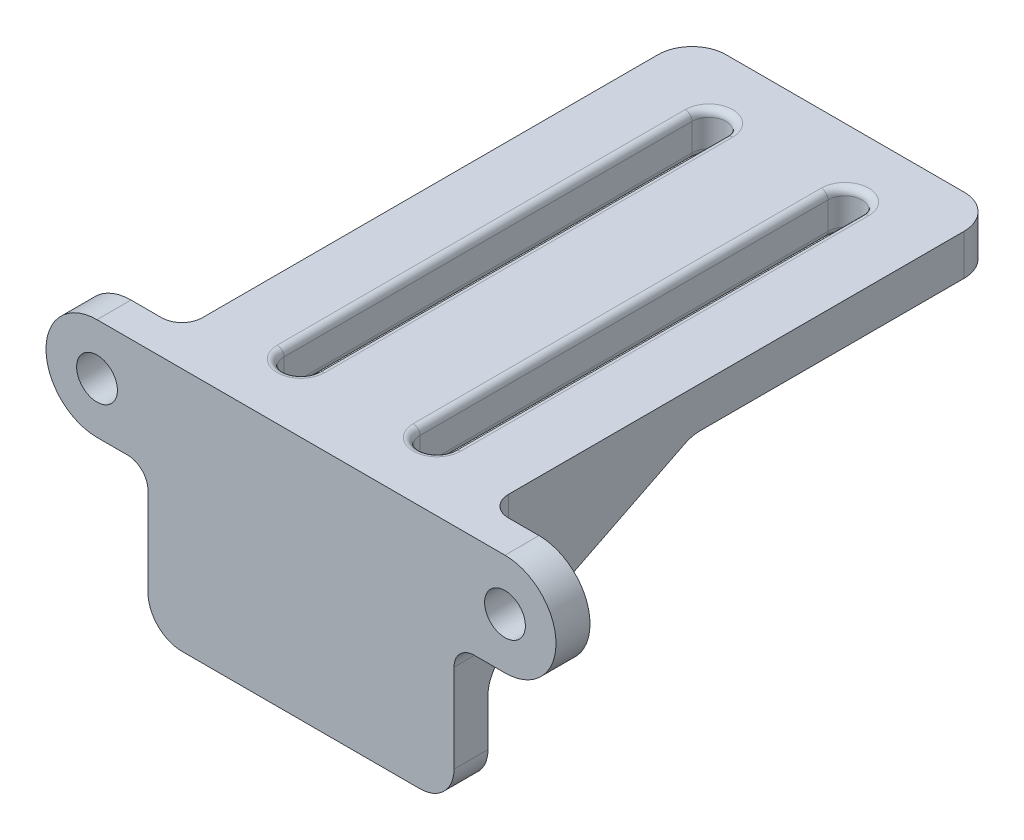
SolidWorks part; units mm, degrees
ref_plane "Piano frontale" through (0, 0, 0) normal (0, 0, 1) x (1, 0, 0)
ref_plane "Piano superiore" through (0, 0, 0) normal (0, 1, 0) x (1, 0, 0)
ref_plane "Piano destro" through (0, 0, 0) normal (1, 0, 0) x (0, 0, -1)
sketch "Schizzo1" plane through (0, 0, 0) normal (0, 0, 1) x (1, 0, 0)
  line L1 (-22.5, 15) -> (22.5, 15)
  line L2 (-22.5, 15) -> (-22.5, -15)
  line L3 (-22.5, -15) -> (22.5, -15)
  line L4 (22.5, 15) -> (22.5, -15)
  line L5 (-22.5, 15) -> (22.5, -15) construction
  line L6 (-22.5, -15) -> (22.5, 15) construction
  point P0 (0, 0)
  dimension "D1" = 45
  dimension "D2" = 30
extrude "Estrusione-Estrusione1" add sketch "Schizzo1" along normal blind 5
sketch "Schizzo4" plane through (0, 15, 0) normal (0, 1, 0) x (1, 0, 0)
  line L1 (22.5, -5) -> (-22.5, -5)
  line L2 (22.5, -5) -> (22.5, 75)
  line L3 (22.5, 75) -> (-22.5, 75)
  line L4 (-22.5, -5) -> (-22.5, 75)
  dimension "D1" = 45
  dimension "D2" = 80
extrude "Estrusione-Estrusione2" add sketch "Schizzo4" along normal blind 6
sketch "Schizzo5" plane through (0, 21, 0) normal (0, 1, 0) x (1, 0, 0)
  line L0 (-10, 37.5433) -> (-10, 50037.5433) construction
  line L1 (0, 75) -> (0, -49925) construction
  line L2 (22.5, 75) -> (-22.5, 75) construction
  line L3 (10, 71.372) -> (10, -49928.628) construction
  line L4 (-20, 35) -> (49980, 35) construction
  line L5 (-22.5, 75) -> (-22.5, -5) construction
  line L6 (-10, 65) -> (-10, 5) construction
  line L7 (-7.5, 65) -> (-7.5, 5)
  line L8 (-12.5, 65) -> (-12.5, 5)
  line L9 (10, 65) -> (10, 5) construction
  line L10 (7.5, 65) -> (7.5, 5)
  line L11 (12.5, 65) -> (12.5, 5)
  arc A0 (-7.5, 65) -> (-12.5, 65) centre (-10, 65) ccw
  arc A1 (-12.5, 5) -> (-7.5, 5) centre (-10, 5) ccw
  arc A2 (7.5, 65) -> (12.5, 65) centre (10, 65) cw
  arc A3 (12.5, 5) -> (7.5, 5) centre (10, 5) cw
  point P6 (0, 75)
  point P13 (-22.5, 35)
  point P16 (-10, 35)
  point P23 (10, 35)
  dimension "D1" = 10
  dimension "D2" = 10
  dimension "D3" = 5
  dimension "D4" = 60
extrude "Taglio-Estrusione1" cut sketch "Schizzo5" against normal through all
fillet "Raccordo1" radius 6 1 edges at (0, 15, 0)
sketch "Schizzo6" plane through (-22.5, 0, 0) normal (-1, 0, 0) x (0, 0, 1)
  line L0 (-30, 15) -> (0, 0)
  line L1 (5, 21) -> (-30, 21)
  line L2 (5, 21) -> (5, 0)
  line L3 (5, 0) -> (-30, 0)
  line L4 (-30, 21) -> (-30, 0)
  line L5 (-75, 15) -> (-6, 15) construction
  line M3 (-75, 15) -> (-6, 15)
  arc M4 (-6, 15) -> (0, 9) centre (-6, 9) cw
  line M5 (0, 9) -> (0, -15)
  line M7 (5, -15) -> (5, 21)
  line M8 (5, 21) -> (-75, 21)
  dimension "D1" = 21
  dimension "D2" = 35
extrude "Estrusione-Estrusione3" add sketch "Schizzo6" against normal blind 3 contours L0 M3 M5 M4 | L4 L3 M8 M3 M4 M5 M7 region at (-22.5, 9.8699, -10.3079) region at (-22.5, 15.1952, -8.3623)
sketch "Schizzo8" plane through (22.5, 0, 0) normal (1, 0, 0) x (0, 0, -1)
  line L0 (0, 0) -> (30, 15)
  line L1 (-5, 21) -> (30, 21)
  line L2 (-5, 21) -> (-5, 0)
  line L3 (-5, 0) -> (30, 0)
  line L4 (30, 21) -> (30, 0)
  line M3 (0, -15) -> (0, 9)
  arc M4 (0, 9) -> (6, 15) centre (6, 9) cw
  line M5 (6, 15) -> (75, 15)
  dimension "D1" = 21
  dimension "D2" = 35
extrude "Estrusione-Estrusione4" add sketch "Schizzo8" against normal blind 3 contours L0 M3 M5 M4 region at (22.5, 9.8699, -10.3079)
fillet "Raccordo2" radius 5 8 edges at (21, 15, -30) (21, 0, 0) (22.5, -15, 2.5) (-22.5, -15, 2.5) (-21, 15, -30) (-21, 0, 0) (-22.5, 18, -75) (22.5, 18, -75)
sketch "Schizzo10" plane through (0, 0, 5) normal (0, 0, 1) x (1, 0, 0)
  line L0 (0, 21) -> (-50000, 21) construction
  line L1 (-22.5, 21) -> (22.5, 21) construction
  line L2 (-2.6049, 13.5) -> (-50002.6049, 13.5) construction
  line L3 (-22.5, 21) -> (-22.5, -10) construction
  line L4 (0, 0) -> (0, 50000) construction
  line L5 (-30, 21) -> (-22.5, 21)
  line L6 (-22.5, 21) -> (-22.5, 6)
  line L7 (-22.5, 6) -> (-30, 6)
  line L8 (22.5, 6) -> (30, 6)
  line L9 (22.5, 21) -> (22.5, 6)
  line L10 (30, 21) -> (22.5, 21)
  arc A0 (-30, 21) -> (-30, 6) centre (-30, 13.5) ccw
  circle A1 centre (-30, 13.5) radius 3
  circle A2 centre (30, 13.5) radius 3
  arc A3 (30, 21) -> (30, 6) centre (30, 13.5) cw
  point P4 (0, 21)
  dimension "D1" = 15
extrude "Estrusione-Estrusione5" add sketch "Schizzo10" against normal blind 5
fillet "Raccordo3" radius 3 4 edges at (22.5, 6, 2.5) (22.5, 13.5, 0) (-22.5, 13.5, 0) (-22.5, 6, 2.5)
fillet "Raccordo4" radius 1 20 edges at (12.5, 14.979, -5.4982) (12.5, 15, -35.5) (10, 15, -67.5) (7.5, 15, -35.5) (7.5, 14.979, -5.4982) (-7.5, 14.979, -5.4982) (-7.5, 15, -35.5) (-10, 15, -67.5) (-12.5, 15, -35.5) (-12.5, 14.979, -5.4982) (-12.5, 21, -35) (-10, 21, -67.5) (-7.5, 21, -35) (10, 21, -67.5) (12.5, 21, -35) (9.6966, 13.8866, -2.5185) (10, 21, -2.5) (-10.3034, 13.8866, -2.5185) (-10, 21, -2.5) (7.5, 21, -35)
